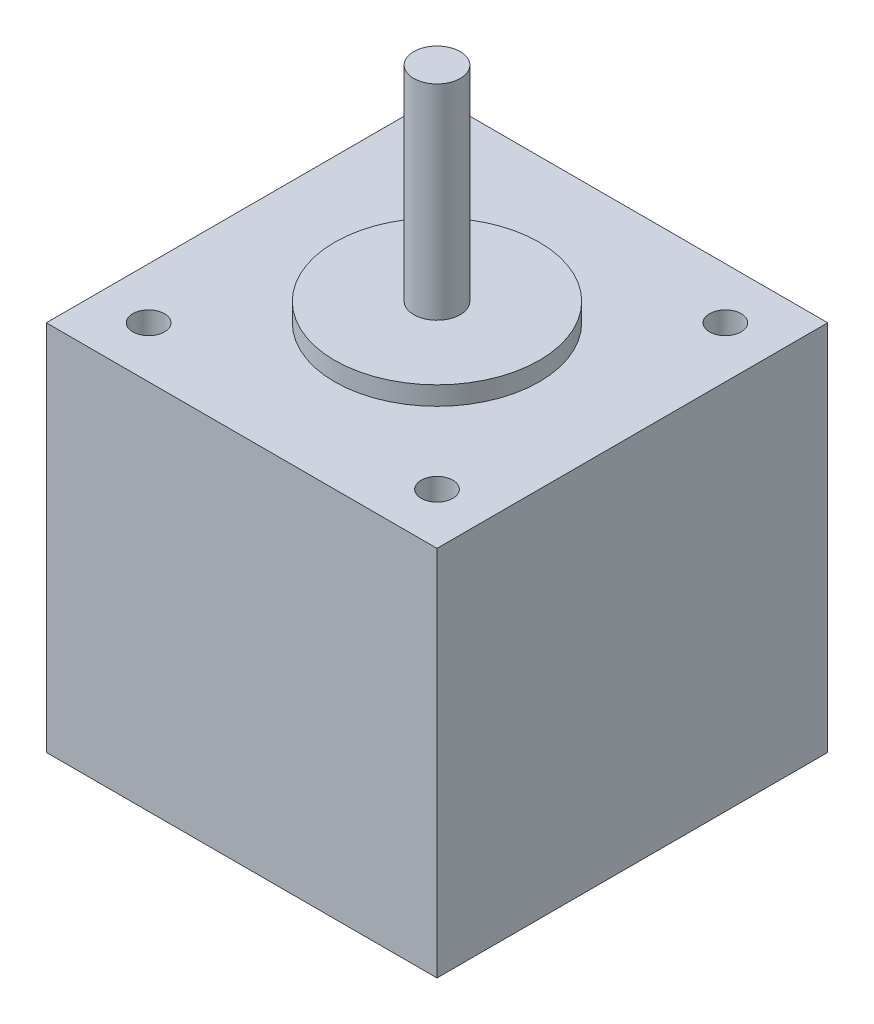
SolidWorks part; units mm, degrees
ref_plane "Front" through (0, 0, 0) normal (0, 0, 1) x (1, 0, 0)
ref_plane "Top" through (0, 0, 0) normal (0, 1, 0) x (1, 0, 0)
ref_plane "Right" through (0, 0, 0) normal (1, 0, 0) x (0, 0, -1)
sketch "Sketch1" plane through (0, 0, 0) normal (0, 1, 0) x (1, 0, 0)
  line L1 (-21, -21) -> (21, -21)
  line L2 (-21, -21) -> (-21, 21)
  line L3 (-21, 21) -> (21, 21)
  line L4 (21, -21) -> (21, 21)
  line L5 (-21, -21) -> (21, 21) construction
  line L6 (-21, 21) -> (21, -21) construction
  line L11 (-14.0711, -14.0711) -> (14.0711, 14.0711) construction
  line L12 (-14.0711, 14.0711) -> (14.0711, -14.0711) construction
  point P0 (0, 0)
  point P6 (0, 0)
  dimension "D1" = 42
extrude "Boss-Extrude1" add sketch "Sketch1" along normal blind 40
sketch "Sketch4" plane through (0, 40, 0) normal (0, 1, 0) x (1, 0, 0)
  line L1 (-15.5, -15.5) -> (15.5, -15.5) construction
  line L2 (-15.5, -15.5) -> (-15.5, 15.5) construction
  line L3 (-15.5, 15.5) -> (15.5, 15.5) construction
  line L4 (15.5, -15.5) -> (15.5, 15.5) construction
  line L5 (-15.5, -15.5) -> (15.5, 15.5) construction
  line L6 (-15.5, 15.5) -> (15.5, -15.5) construction
  circle A1 centre (-15.5, 15.5) radius 1.7
  circle A2 centre (15.5, 15.5) radius 1.7
  circle A3 centre (-15.5, -15.5) radius 1.7
  circle A4 centre (15.5, -15.5) radius 1.7
  point P0 (0, 0)
  dimension "D2" = 3.4
  dimension "D1" = 31
extrude "Cut-Extrude1" cut sketch "Sketch4" against normal blind 4.5
sketch "Sketch2" plane through (0, 40, 0) normal (0, 1, 0) x (1, 0, 0)
  circle A0 centre (0, 0) radius 11
  dimension "D1" = 22
extrude "Boss-Extrude2" add sketch "Sketch2" along normal blind 2
sketch "Sketch3" plane through (0, 42, 0) normal (0, 1, 0) x (1, 0, 0)
  circle A0 centre (0, 0) radius 2.5
  dimension "D1" = 5
extrude "Boss-Extrude3" add sketch "Sketch3" along normal blind 22
